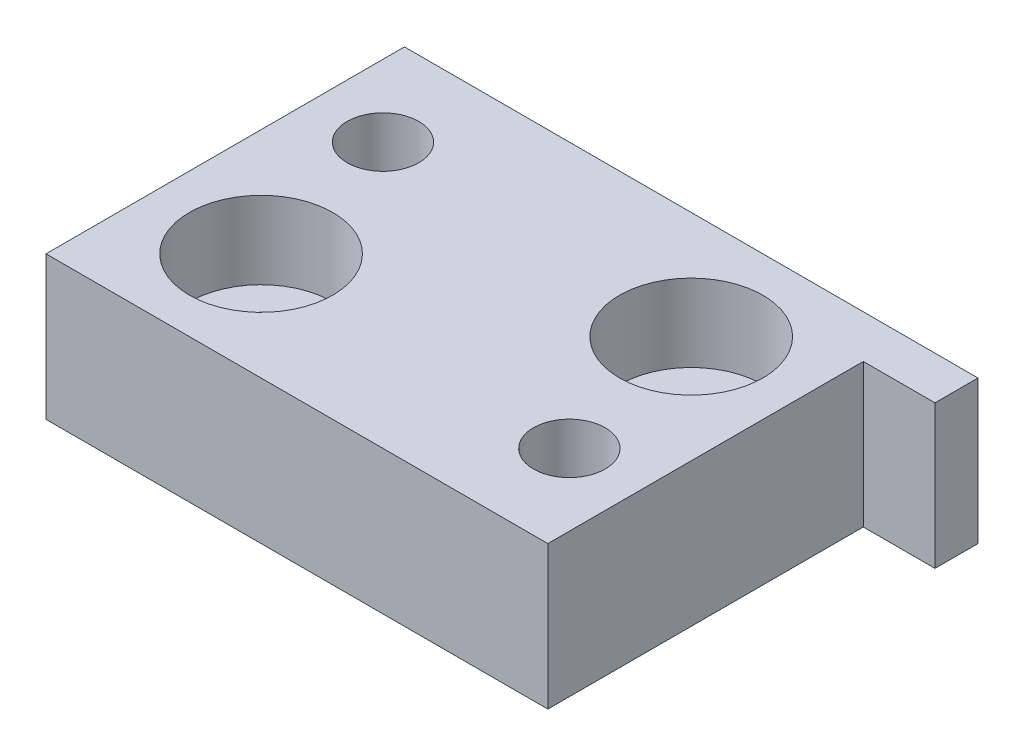
SolidWorks part; units mm, degrees
material "Plain Carbon Steel"
ref_plane "Front Plane" through (0, 0, 0) normal (0, 0, 1) x (1, 0, 0)
ref_plane "Top Plane" through (0, 0, 0) normal (0, 1, 0) x (1, 0, 0)
ref_plane "Right Plane" through (0, 0, 0) normal (1, 0, 0) x (0, 0, -1)
sketch "Sketch1" plane through (0, 0, 0) normal (0, 1, 0) x (1, 0, 0)
  line L1 (-20, -12.5) -> (20, -12.5)
  line L2 (-20, -12.5) -> (-20, 12.5)
  line L3 (-20, 12.5) -> (20, 12.5)
  line L4 (20, -12.5) -> (20, 12.5)
  line L5 (-20, -12.5) -> (20, 12.5) construction
  line L6 (-20, 12.5) -> (20, -12.5) construction
  point P0 (0, 0)
  dimension "D1" = 40
  dimension "D2" = 25
extrude "Boss-Extrude1" add sketch "Sketch1" along normal blind 10
sketch "Sketch3" plane through (0, 10, 0) normal (0, 1, 0) x (1, 0, 0)
  line L0 (20, 12.5) -> (-20, 12.5) construction
  line L1 (20, -12.5) -> (15, -12.5)
  line L2 (20, -12.5) -> (20, 9.5)
  line L3 (20, 9.5) -> (15, 9.5)
  line L4 (15, -12.5) -> (15, 9.5)
  dimension "D1" = 5
  dimension "D2" = 3
extrude "Cut-Extrude2" cut sketch "Sketch3" against normal up to next
hole_wizard "Ø5.0mm Dowel Hole1" positions "Sketch9" profile "Sketch5" hole size "Ø5.0" standard "ISO" end condition through all
sketch "Sketch9" plane through (0, 10, 0) normal (0, 1, 0) x (1, 0, 0)
  line L4 (-2.5, -12.5) -> (-2.5, 12.5) construction
  line L5 (-20, -12.5) -> (15, -12.5) construction
  line L6 (20, 12.5) -> (-20, 12.5) construction
  line L7 (-20, 0) -> (15, 0) construction
  line L8 (-20, 12.5) -> (-20, -12.5) construction
  line L9 (15, 9.5) -> (15, -12.5) construction
  point P31 (10, -6)
  point P33 (-15, 6)
  dimension "D1" = 25
  dimension "D2" = 12
  dimension "D3" = 6
  dimension "D4" = 12.5
sketch "Sketch5" plane through (-15, 10, -6) normal (1, 0, 0) x (0, 0, 1)
  line L0 (0, 0) -> (0, 10)
  line L1 (0, 10) -> (2.5, 10)
  line L2 (2.5, 10) -> (2.5, 0)
  line L5 (2.5, 0) -> (0, 0)
  line L11 (0, -6.35) -> (0, 107.95) construction
  dimension "Thru Hole Dia." = 5
  dimension "Thru Hole Depth" = 10
hole_wizard "CBORE for M5 Hex Socket Head Cap Screw1" positions "Sketch14" profile "Sketch11" counterbore size "M5" standard "ISO" end condition through all
sketch "Sketch14" plane through (0, 10, 0) normal (0, 1, 0) x (1, 0, 0)
  line L0 (-20, 0) -> (15, 0) construction
  line L1 (-20, 12.5) -> (-20, -12.5) construction
  line L2 (15, 9.5) -> (15, -12.5) construction
  line L4 (-2.5, -12.5) -> (-2.5, 12.5) construction
  line L5 (-20, -12.5) -> (15, -12.5) construction
  line L6 (100, 12.5) -> (-20, 12.5) construction
  point P0 (-12.5, -5)
  point P2 (7.5, 5)
  dimension "D1" = 10
  dimension "D2" = 5
  dimension "D3" = 20
  dimension "D4" = 10
sketch "Sketch11" plane through (-12.5, 10, 5) normal (1, 0, 0) x (0, 0, 1)
  line L0 (0, 0) -> (0, 10)
  line L1 (0, 10) -> (2.65, 10)
  line L3 (2.65, 10) -> (2.65, 5.4)
  line L4 (2.65, 5.4) -> (5, 5.4)
  line L5 (5, 5.4) -> (5, 0)
  line L7 (5, 0) -> (0, 0)
  line L11 (0, -6.35) -> (0, 107.95) construction
  dimension "Thru Hole Dia." = 5.3
  dimension "Thru Hole Depth" = 10
  dimension "C'Bore Dia." = 10
  dimension "C'Bore Depth" = 5.4
